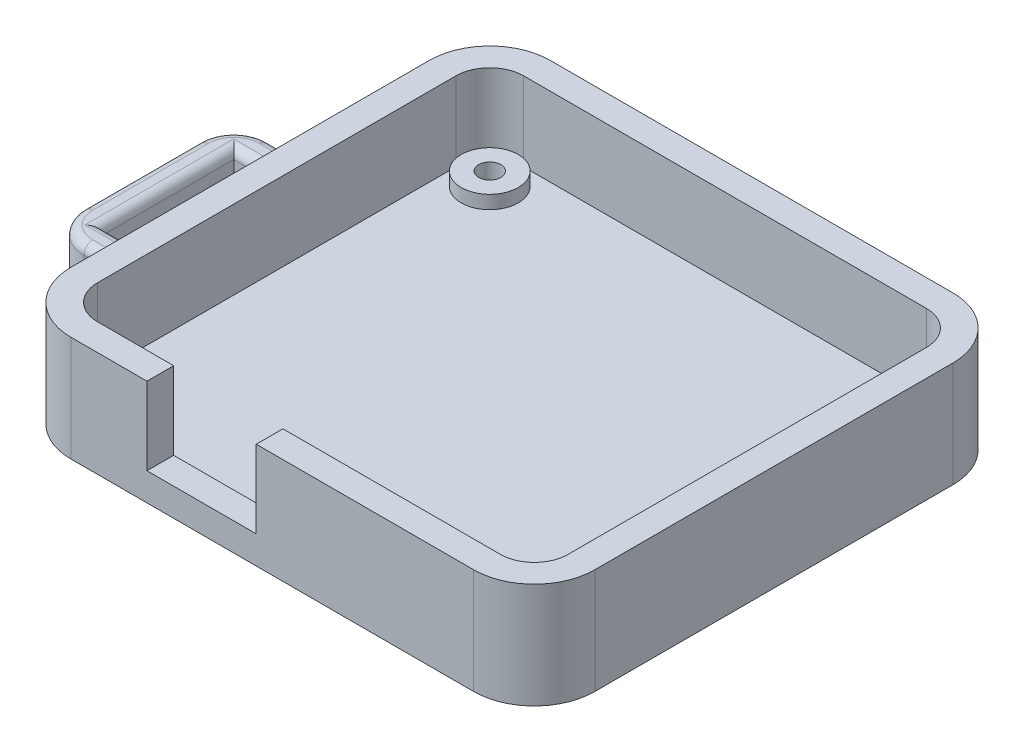
SolidWorks part; units mm, degrees
ref_plane "Front Plane" through (0, 0, 0) normal (0, 0, 1) x (1, 0, 0)
ref_plane "Top Plane" through (0, 0, 0) normal (0, 1, 0) x (1, 0, 0)
ref_plane "Right Plane" through (0, 0, 0) normal (1, 0, 0) x (0, 0, -1)
sketch "Sketch1" plane through (0, 0, 0) normal (0, 1, 0) x (1, 0, 0)
  line L0 (3.81, 3) -> (49.09, 3)
  line L1 (3.81, 0) -> (49.09, 0)
  line L2 (0, -3.81) -> (0, -44.09)
  line L3 (3.81, -47.9) -> (49.09, -47.9)
  line L4 (52.9, -3.81) -> (52.9, -44.09)
  line L5 (55.9, -3.81) -> (55.9, -44.09)
  line L6 (3.81, -50.9) -> (49.09, -50.9)
  line L7 (-3, -3.81) -> (-3, -44.09)
  arc A0 (52.9, -3.81) -> (49.09, 0) centre (49.09, -3.81) ccw
  arc A1 (0, -3.81) -> (3.81, 0) centre (3.81, -3.81) cw
  arc A2 (3.81, -47.9) -> (0, -44.09) centre (3.81, -44.09) cw
  arc A3 (52.9, -44.09) -> (49.09, -47.9) centre (49.09, -44.09) cw
  circle A4 centre (49.09, -44.09) radius 1.25
  circle A5 centre (3.81, -44.09) radius 1.25
  circle A6 centre (3.81, -3.81) radius 1.25
  circle A7 centre (49.09, -3.81) radius 1.25
  arc A8 (55.9, -3.81) -> (49.09, 3) centre (49.09, -3.81) ccw
  arc A9 (55.9, -44.09) -> (49.09, -50.9) centre (49.09, -44.09) cw
  arc A10 (3.81, -50.9) -> (-3, -44.09) centre (3.81, -44.09) cw
  arc A11 (-3, -3.81) -> (3.81, 3) centre (3.81, -3.81) cw
  circle A12 centre (3.81, -3.81) radius 3.21
  circle A13 centre (49.09, -3.81) radius 3.21
  circle A14 centre (49.09, -44.09) radius 3.21
  circle A15 centre (3.81, -44.09) radius 3.21
  point P7 (52.9, 0)
  point P10 (0, 0)
  point P15 (52.9, -47.9)
  dimension "D3" = 3.81
  dimension "D4" = 3.81
  dimension "D5" = 3.81
  dimension "D6" = 3.81
  dimension "D7" = 3
  dimension "D8" = 2.5
  dimension "D9" = 2.5
  dimension "D10" = 2.5
  dimension "D11" = 2.5
  dimension "D12" = 6.42
  dimension "D13" = 6.42
  dimension "D14" = 6.42
  dimension "D15" = 6.42
  dimension "D1" = 52.9
  dimension "D2" = 47.9
extrude "Boss-Extrude1" add sketch "Sketch1" against normal blind 3 contours L7 A10 L6 A9 L5 A8 L0 A11
extrude "Cut-Extrude1" cut sketch "Sketch1<3>" against normal up to next contours A6 | A5 | A4 | A7 region at (49.09, 0, 44.09) region at (3.81, 0, 44.09) region at (3.81, 0, 3.81) region at (49.09, 0, 3.81)
sketch "Sketch1<3>" plane through (0, 0, 0) normal (0, 1, 0) x (1, 0, 0) same geometry as "Sketch1"
extrude "Boss-Extrude2" add sketch "Sketch1<4>" along normal blind 8.86 contours A11 L7 A10 L6 A9 L5 A8 L0 L4 A3 L3 A2 L2 A1 L1 A0 region at (26.45, 0, -2.2016)
sketch "Sketch1<4>" plane through (0, 0, 0) normal (0, 1, 0) x (1, 0, 0) same geometry as "Sketch1"
extrude "Boss-Extrude3" add sketch "Sketch1<5>" along normal blind 1.5 contours A13 A7 | A14 A4 | A15 A5 | A12 A6 region at (0.6908, 0, 3.81) region at (45.9708, 0, 3.81) region at (45.9708, 0, 44.09) region at (0.6908, 0, 44.09)
sketch "Sketch1<5>" plane through (0, 0, 0) normal (0, 1, 0) x (1, 0, 0) same geometry as "Sketch1"
sketch "Sketch2" plane through (0, 0, 50.9) normal (0, 0, 1) x (1, 0, 0)
  line L0 (3.81, -3) -> (49.09, -3) construction
  line L1 (12.36, 8.865) -> (24.64, 8.865)
  line L2 (12.36, 8.865) -> (12.36, 0.135)
  line L3 (12.36, 0.135) -> (24.64, 0.135)
  line L4 (24.64, 8.865) -> (24.64, 0.135)
  line L5 (-3, -3) -> (-3, 8.86) construction
  dimension "D1" = 3.135
  dimension "D2" = 8.73
  dimension "D3" = 12.28
  dimension "D4" = 15.36
extrude "Cut-Extrude2" cut sketch "Sketch2" against normal blind 3
sketch "Sketch7" plane through (0, -3, 0) normal (0, -1, 0) x (-1, 0, 0)
  line L0 (3, -3.81) -> (3, -44.09) construction
  line L1 (3, -34.325) -> (11.3, -34.325)
  line L2 (3, -34.325) -> (3, -13.575)
  line L3 (3, -13.575) -> (11.3, -13.575)
  line L4 (15.2, -30.425) -> (15.2, -17.475)
  line L5 (-3.81, -50.9) -> (-49.09, -50.9) construction
  line L7 (12.2, -31.325) -> (5, -31.325)
  line L8 (12.2, -31.325) -> (12.2, -16.575)
  line L9 (12.2, -16.575) -> (5, -16.575)
  line L10 (5, -31.325) -> (5, -16.575)
  arc A0 (15.2, -30.425) -> (11.3, -34.325) centre (11.3, -30.425) cw
  arc A1 (11.3, -13.575) -> (15.2, -17.475) centre (11.3, -17.475) cw
  point P10 (15.2, -34.325)
  point P13 (15.2, -13.575)
  dimension "D5" = 3.9
  dimension "D6" = 3.9
  dimension "D1" = 20.75
  dimension "D2" = 12.2
  dimension "D3" = 0
  dimension "D4" = 16.575
  dimension "D7" = 14.75
  dimension "D8" = 3
  dimension "D9" = 7.2
  dimension "D10" = 3
extrude "Boss-Extrude6" add sketch "Sketch7" against normal blind 5
fillet "Fillet3" radius 1 9 edges at (-7.15, 2, 34.325) (-14.0577, 2, 33.1827) (-15.2, 2, 23.95) (-14.0577, 2, 14.7173) (-7.15, 2, 13.575) (-8.6, 2, 16.575) (-5, 2, 23.95) (-12.2, 2, 23.95) (-8.6, 2, 31.325)
